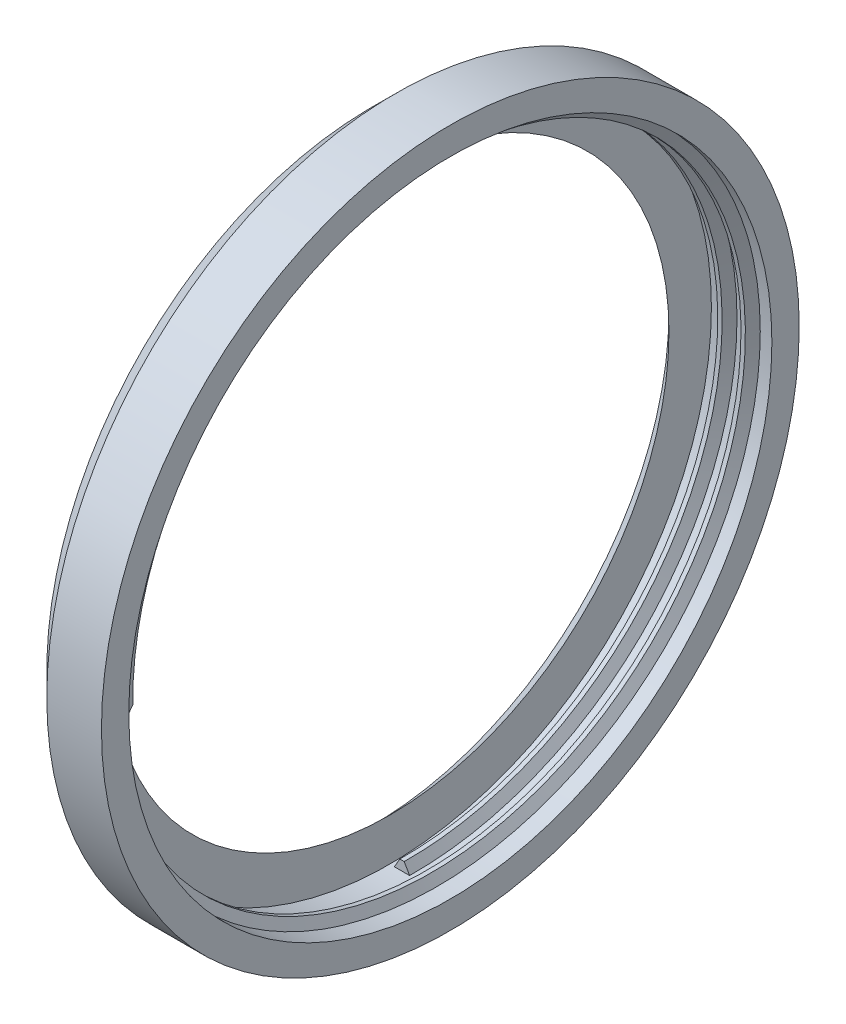
SolidWorks part; units mm, degrees
ref_plane "Front Plane" through (0, 0, 0) normal (0, 0, 1) x (1, 0, 0)
ref_plane "Top Plane" through (0, 0, 0) normal (0, 1, 0) x (1, 0, 0)
ref_plane "Right Plane" through (0, 0, 0) normal (1, 0, 0) x (0, 0, -1)
sketch "Sketch1" plane through (0, 0, 0) normal (1, 0, 0) x (0, 0, -1)
  circle A0 centre (0, 0) radius 24
  circle A1 centre (0, 0) radius 30
  dimension "D1" = 6
  dimension "D2" = 60
extrude "Boss-Extrude1" add sketch "Sketch1" along normal blind 1.5
sketch "Sketch2" plane through (1.5, 0, 0) normal (1, 0, 0) x (0, 0, -1)
  circle A2 centre (0, 0) radius 27.65
  circle A3 centre (0, 0) radius 27.65
  circle M2 centre (0, 0) radius 30
  dimension "D1" = 2.35
extrude "Boss-Extrude2" add sketch "Sketch2" along normal blind 5.2 contours A3 M2 region at (1.5, 0, 29.1515)
thread "Thread1" pitch 1.5 method extrude profile "Thread Profile1" start angle 0, offset 0, length 3.5, pitch 2, diameter 55.3
ref_plane "Plane1" through (6.7, 0, 27.65) normal (0, -1, 0) x (0, 0, 1)
sketch "Thread Profile1" plane through (6.7, 0, 27.65) normal (0, -1, 0) x (0, 0, 1)
  line L0 (0, 0) -> (0, 1.5) construction
  line L11 (0, 0) -> (0, 1.3125)
  line L12 (0, 1.3125) -> (-0.8119, 0.8437)
  line L13 (-0.8119, 0.8437) -> (-0.8119, 0.4687)
  line L15 (-0.8119, 0.4687) -> (0, 0)
  line L17 (-0.8119, 0.6562) -> (0, 0.6562) construction
  point P2 (0, 0)
  dimension "Pitch" = 1.5
  dimension "Profile_Angle" = 60
  dimension "Profile_Land" = 0.375
  dimension "Profile_Height" = 0.8119
chamfer "Chamfer1" distance 2 angle 45 1 edges at (0, 0, -30)
chamfer "Chamfer2" distance 1.5 angle 45 1 edges at (0, 0, -24)
